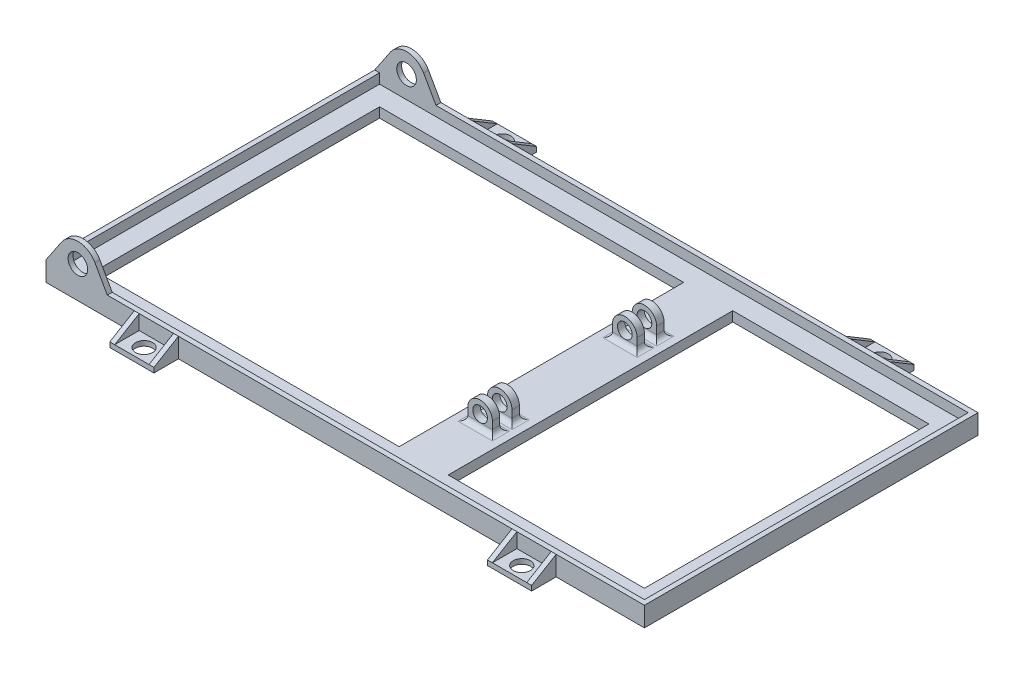
SolidWorks part; units mm, degrees
ref_plane "前基準面" through (0, 0, 0) normal (0, 0, 1) x (1, 0, 0)
ref_plane "上基準面" through (0, 0, 0) normal (0, 1, 0) x (1, 0, 0)
ref_plane "右基準面" through (0, 0, 0) normal (1, 0, 0) x (0, 0, -1)
sketch "草圖2" plane through (0, 0, 0) normal (0, 1, 0) x (1, 0, 0)
  line L1 (-60, -33) -> (60, -33)
  line L2 (-60, -33) -> (-60, 33)
  line L3 (-60, 33) -> (60, 33)
  line L4 (60, -33) -> (60, 33)
  line L5 (-60, -33) -> (60, 33) construction
  line L6 (-60, 33) -> (60, -33) construction
  line L7 (-56, -29) -> (56, -29)
  line L8 (-56, -29) -> (-56, 29)
  line L9 (-56, 29) -> (56, 29)
  line L10 (56, -29) -> (56, 29)
  line L11 (-56, -29) -> (56, 29) construction
  line L12 (-56, 29) -> (56, -29) construction
  point P0 (0, 0)
  point P6 (0, 0)
  dimension "D1" = 66
  dimension "D2" = 120
  dimension "D3" = 4
  dimension "D4" = 4
extrude "填料-伸長1" add sketch "草圖2" along normal blind 2
extrude "伸長-薄件1" add sketch "草圖2<2>" along normal blind 4 thin contours L3 L4 L1 L2 thin type one direction wall 1
sketch "草圖2<2>" plane through (0, 0, 0) normal (0, 1, 0) x (1, 0, 0) same geometry as "草圖2"
sketch "草圖3" plane through (0, 0, 34) normal (0, 0, 1) x (1, 0, 0)
  line L0 (-61, 4) -> (-57.8198, 8.7314)
  line L1 (-51.0152, 8.4636) -> (-48.5, 4)
  line L2 (-61, 4) -> (61, 4) construction
  line L3 (-61, 4) -> (-48.5, 4)
  line L4 (-61, 4) -> (-61, 0) construction
  arc A0 (-57.8198, 8.7314) -> (-51.0152, 8.4636) centre (-54.5, 6.5) cw
  circle A1 centre (-54.5, 6.5) radius 2
  dimension "D1" = 4
  dimension "D4" = 6.5
  dimension "D5" = 4
  dimension "D2" = 12.5
  dimension "D3" = 2.5
extrude "填料-伸長2" add sketch "草圖3" against normal blind 1
mirror "鏡射1" about plane through (0, 0, 0) normal (0, 0, 1) of "填料-伸長2"
sketch "草圖4" plane through (0, 0, 34) normal (0, 0, 1) x (1, 0, 0)
  line L6 (-61, 0) -> (61, 0) construction
  line L7 (6, 0) -> (16, 0)
  line L8 (6, 0) -> (6, 2)
  line L9 (6, 2) -> (16, 2)
  line L10 (16, 0) -> (16, 2)
  dimension "D1" = 6
  dimension "D2" = 2
  dimension "D3" = 10
extrude "填料-伸長3" add sketch "草圖4" against normal blind 68
sketch "草圖5" plane through (0, 0, 0) normal (0, 0, 1) x (1, 0, 0)
  line L0 (8.5, 4.5) -> (8.5, 2)
  line L2 (13.5, 4.5) -> (13.5, 2)
  line L3 (13.5, 2) -> (8.5, 2)
  line L4 (6, 2) -> (-56, 2) construction
  line L5 (6, 0) -> (6, 2) construction
  circle A1 centre (11, 4.5) radius 1.5
  arc A2 (13.5, 4.5) -> (8.5, 4.5) centre (11, 4.5) ccw
  point P13 (6, 1)
  dimension "D3" = 2.5
  dimension "D4" = 3
  dimension "D1" = 2.5
  dimension "D2" = 5
extrude "填料-伸長4" add sketch "草圖5" along normal blind 1.5 from offset 12
extrude "填料-伸長6" add sketch "草圖5<3>" along normal blind 1.5 from offset 16
sketch "草圖5<3>" plane through (0, 0, 0) normal (0, 0, 1) x (1, 0, 0) same geometry as "草圖5"
fillet "圓角2" radius 1 8 edges at (11, 2, 16) (11, 2, 12) (13.5, 2, 12.75) (13.5, 2, 16.75) (8.5, 2, 16.75) (11, 2, 17.5) (8.5, 2, 12.75) (11, 2, 13.5)
mirror "鏡射3" about plane through (0, 0, 0) normal (0, 0, 1) of "填料-伸長6", "圓角2", "填料-伸長4"
sketch "草圖7" plane through (0, 0, 0) normal (0, -1, 0) x (1, 0, 0)
  line L0 (-61, 34) -> (61, 34) construction
  line L1 (-43, 34) -> (-34, 34) construction
  line L2 (-43, 34) -> (-43, 39) construction
  line L3 (-43, 39) -> (-34, 39) construction
  line L4 (-34, 34) -> (-34, 39) construction
  line L5 (61, 34) -> (61, -34) construction
  line L6 (34, 34) -> (43, 34)
  line L7 (34, 34) -> (34, 39)
  line L8 (34, 39) -> (43, 39)
  line L9 (43, 34) -> (43, 39)
  line L10 (-61, 0) -> (61, 0) construction
  line L11 (-61, 34) -> (-61, -34) construction
  line L12 (0, 0) -> (0, 41.0055) construction
  line L13 (-34, 36.5) -> (-43, 36.5) construction
  line L14 (-38.5, 36.5) -> (-38.5, 23.7535) construction
  dimension "D1" = 5
  dimension "D2" = 9
  dimension "D3" = 38.5
extrude "填料-伸長7" add sketch "草圖7" against normal blind 1
sketch "草圖8" plane through (43, 0, 0) normal (1, 0, 0) x (0, 0, -1)
  line L0 (-39, 1) -> (-34, 4)
  line L1 (-34, 4) -> (-34, 1)
  line L2 (-34, 1) -> (-39, 1)
extrude "填料-伸長8" add sketch "草圖8" against normal blind 1
sketch "草圖9" plane through (34, 0, 0) normal (-1, 0, 0) x (0, 0, 1)
  line L3 (39, 1) -> (34, 4)
  line L4 (34, 4) -> (34, 1)
  line L5 (34, 1) -> (39, 1)
  line L6 (39, 1) -> (34, 4)
  line L7 (34, 4) -> (34, 1)
  line L8 (34, 1) -> (39, 1)
  dimension "D1" = 0
extrude "填料-伸長9" add sketch "草圖9" against normal blind 1
sketch "草圖10" plane through (0, 1, 0) normal (0, 1, 0) x (1, 0, 0)
  line L0 (38.5, -34) -> (38.5, -39) construction
  line L1 (35, -34) -> (42, -34) construction
  line L2 (42, -39) -> (35, -39) construction
  circle A0 centre (38.5, -36.5) radius 1.75
  dimension "D1" = 3.5
extrude "除料-伸長1" cut sketch "草圖10" against normal up to next
mirror "鏡射5" about plane through (0, 0, 0) normal (0, 0, 1) of "除料-伸長1", "填料-伸長9", "填料-伸長8", "填料-伸長7"
mirror "鏡射6" about plane through (0, 0, 0) normal (1, 0, 0) of "鏡射5", "除料-伸長1", "填料-伸長9", "填料-伸長8", "填料-伸長7"
